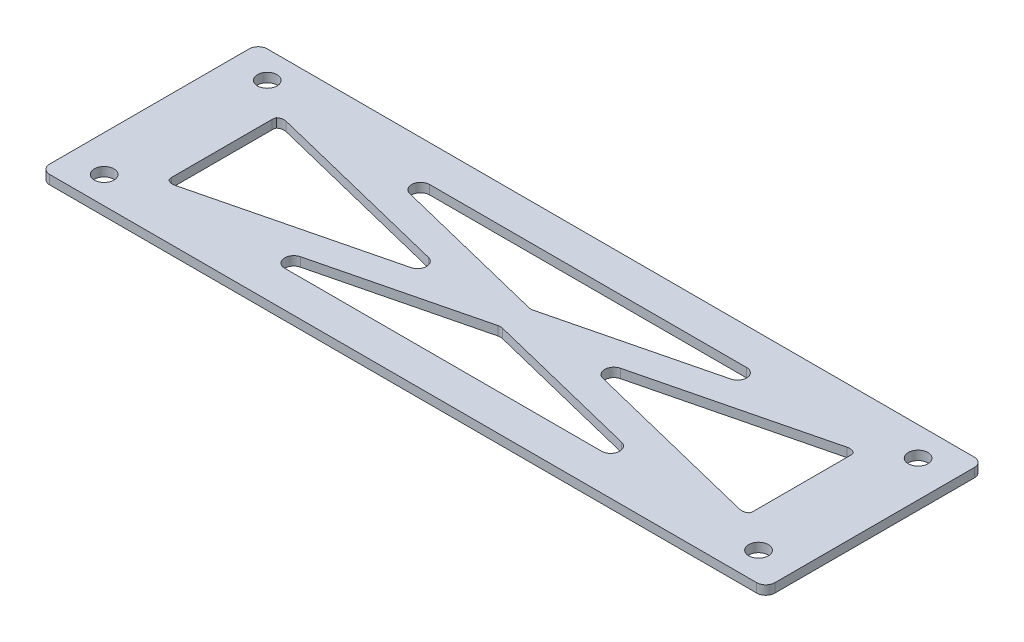
SolidWorks part; units mm, degrees
ref_plane "Front Plane" through (0, 0, 0) normal (0, 0, 1) x (1, 0, 0)
ref_plane "Top Plane" through (0, 0, 0) normal (0, 1, 0) x (1, 0, 0)
ref_plane "Right Plane" through (0, 0, 0) normal (1, 0, 0) x (0, 0, -1)
sketch "Sketch1" plane through (0, 0, 0) normal (0, 1, 0) x (1, 0, 0)
  line L0 (-114.3, 0) -> (114.3, 0) construction
  line L1 (-127, -38.1) -> (127, -38.1)
  line L2 (-127, -38.1) -> (-127, 38.1)
  line L3 (-127, 38.1) -> (127, 38.1)
  line L4 (127, -38.1) -> (127, 38.1)
  line L5 (-127, -38.1) -> (127, 38.1) construction
  line L6 (-127, 38.1) -> (127, -38.1) construction
  line L7 (-114.3, 28.575) -> (-114.3, -28.575) construction
  line L8 (114.3, 27.94) -> (114.3, -27.94) construction
  circle A3 centre (-114.3, 28.575) radius 3.429
  circle A4 centre (-114.3, -28.575) radius 3.429
  circle A5 centre (114.3, 27.94) radius 3.429
  circle A6 centre (114.3, -27.94) radius 3.429
  point P0 (0, 0)
  point P8 (0, 0)
  point P13 (-114.3, 0)
  point P18 (114.3, 0)
  dimension "D4" = 57.15
  dimension "D5" = 6.858
  dimension "D1" = 254
  dimension "D2" = 76.2
  dimension "D3" = 228.6
  dimension "D6" = 55.88
extrude "Boss-Extrude1" add sketch "Sketch1" along normal blind 3.175
fillet "Fillet1" radius 3.175 4 edges at (127, 1.5875, -38.1) (127, 1.5875, 38.1) (-127, 1.5875, -38.1) (-127, 1.5875, 38.1)
sketch "Sketch2" plane through (0, 3.175, 0) normal (0, 1, 0) x (1, 0, 0)
  line L0 (-101.6, 25.4) -> (-101.6, -25.4)
  line L1 (101.6, -25.4) -> (101.6, 25.4)
  line L12 (-114.3, 28.575) -> (114.3, -27.94) construction
  line L13 (-114.3, -28.575) -> (114.3, 27.94) construction
  line L14 (-115.5192, 23.6435) -> (113.0808, -32.8715)
  line L15 (-113.0808, -33.5065) -> (115.5192, 23.0085)
  line L16 (-114.3, 25.4) -> (-114.3, -25.4)
  line L17 (-114.3, -25.4) -> (114.3, -25.4)
  line L18 (114.3, -25.4) -> (114.3, 25.4)
  line L19 (114.3, 25.4) -> (-114.3, 25.4)
  line L20 (-114.3, 25.4) -> (-114.3, -25.4)
  line L21 (-114.3, -25.4) -> (114.3, -25.4)
  line L22 (114.3, -25.4) -> (114.3, 25.4)
  line L23 (114.3, 25.4) -> (-114.3, 25.4)
  line L24 (-113.0808, 33.5065) -> (115.5192, -23.0085)
  line L25 (-115.5192, -23.6435) -> (113.0808, 32.8715)
  circle A18 centre (-114.3, 28.575) radius 16.129
  circle A19 centre (-114.3, 28.575) radius 16.129
  circle A24 centre (114.3, 27.94) radius 16.129
  circle A25 centre (114.3, 27.94) radius 16.129
  circle A27 centre (114.3, -27.94) radius 16.129
  circle A28 centre (114.3, -27.94) radius 16.129
  circle A30 centre (-114.3, -28.575) radius 16.129
  circle A31 centre (-114.3, -28.575) radius 16.129
  dimension "D7" = 5.08
  dimension "D1" = 12.7
  dimension "D2" = 12.7
  dimension "D4" = 12.7
  dimension "D5" = 12.7
  dimension "D6" = 12.7
  dimension "D8" = 5.08
  dimension "D9" = 12.7
extrude "Cut-Extrude1" cut sketch "Sketch2" against normal through all contours L0 L25 L14 | L25 L23 L24 | L15 L24 L1 | L15 L21 L14 region at (-74.336, 3.175, 0) region at (1.2843, 3.175, -18.6776) region at (1.2843, 3.175, 18.6776) region at (75.1914, 3.175, 0)
fillet "Fillet3" radius 3.175 16 edges at (100.6585, 1.5875, 19.3346) (22.4512, 1.5875, 0) (100.6585, 1.5875, -19.3346) (82.8589, 1.5875, -25.4) (82.8589, 1.5875, 25.4) (-80.2904, 1.5875, 25.4) (-80.2904, 1.5875, -25.4) (-19.8827, 1.5875, 0) (-100.6585, 1.5875, 19.9696) (-100.6585, 1.5875, -19.9696) (1.2843, 1.5875, -5.2329) (1.2843, 1.5875, 5.2329) (101.6, 1.5875, -17.9974) (101.6, 1.5875, 17.9974) (-101.6, 1.5875, 18.6324) (-101.6, 1.5875, -18.6324)
